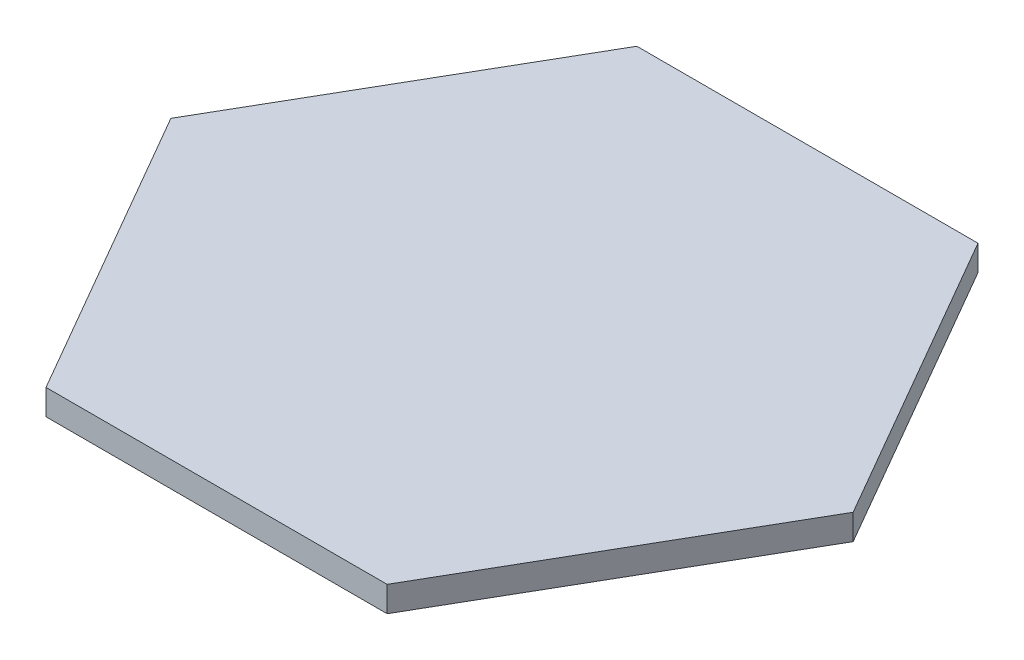
SolidWorks part; units mm, degrees
ref_plane "Front Plane" through (0, 0, 0) normal (0, 0, 1) x (1, 0, 0)
ref_plane "Top Plane" through (0, 0, 0) normal (0, 1, 0) x (1, 0, 0)
ref_plane "Right Plane" through (0, 0, 0) normal (1, 0, 0) x (0, 0, -1)
sketch "Sketch1" plane through (0, 0, 0) normal (0, 1, 0) x (1, 0, 0)
  line L1 (-16.5, -28.5788) -> (16.5, -28.5788) construction
  line L2 (16.5, -28.5788) -> (33, 0) construction
  line L3 (33, 0) -> (16.5, 28.5788) construction
  line L4 (16.5, 28.5788) -> (-16.5, 28.5788) construction
  line L5 (-16.5, 28.5788) -> (-33, 0) construction
  line L6 (-33, 0) -> (-16.5, -28.5788) construction
  line L7 (-33, -57.1577) -> (33, -57.1577) construction
  line L8 (33, -57.1577) -> (66, 0) construction
  line L9 (66, 0) -> (33, 57.1577) construction
  line L10 (33, 57.1577) -> (-33, 57.1577) construction
  line L11 (-33, 57.1577) -> (-66, 0) construction
  line L12 (-66, 0) -> (-33, -57.1577) construction
  line L13 (-42.5263, -73.6577) -> (42.5263, -73.6577)
  line L14 (42.5263, -73.6577) -> (85.0526, 0)
  line L15 (85.0526, 0) -> (42.5263, 73.6577)
  line L16 (42.5263, 73.6577) -> (-42.5263, 73.6577)
  line L17 (-42.5263, 73.6577) -> (-85.0526, 0)
  line L18 (-85.0526, 0) -> (-42.5263, -73.6577)
  circle A0 centre (0, 0) radius 33 construction
  circle A1 centre (0, 0) radius 16.5 construction
  circle A2 centre (-16.5, 28.5788) radius 16.5 construction
  circle A3 centre (16.5, 28.5788) radius 16.5 construction
  circle A4 centre (33, 0) radius 16.5 construction
  circle A5 centre (16.5, -28.5788) radius 16.5 construction
  circle A6 centre (-16.5, -28.5788) radius 16.5 construction
  circle A7 centre (-33, 0) radius 16.5 construction
  circle A8 centre (0, 0) radius 57.1577 construction
  circle A9 centre (-49.5, 28.5788) radius 16.5 construction
  circle A10 centre (0, 57.1577) radius 16.5 construction
  circle A11 centre (49.5, 28.5788) radius 16.5 construction
  circle A12 centre (49.5, -28.5788) radius 16.5 construction
  circle A13 centre (0, -57.1577) radius 16.5 construction
  circle A14 centre (-49.5, -28.5788) radius 16.5 construction
  circle A15 centre (-66, 0) radius 16.5 construction
  circle A16 centre (-33, 57.1577) radius 16.5 construction
  circle A17 centre (33, 57.1577) radius 16.5 construction
  circle A18 centre (66, 0) radius 16.5 construction
  circle A19 centre (33, -57.1577) radius 16.5 construction
  circle A20 centre (-33, -57.1577) radius 16.5 construction
  circle A21 centre (0, 0) radius 73.6577 construction
  point P24 (0, 0)
  point P44 (0, 0)
  point P56 (0, 0)
  dimension "D1" = 66
  dimension "D2" = 33
  dimension "D4" = 33
  dimension "D5" = 6
  dimension "D3" = 6
  dimension "D6" = 6
extrude "Boss-Extrude1" add sketch "Sketch1" along normal blind 6.35
